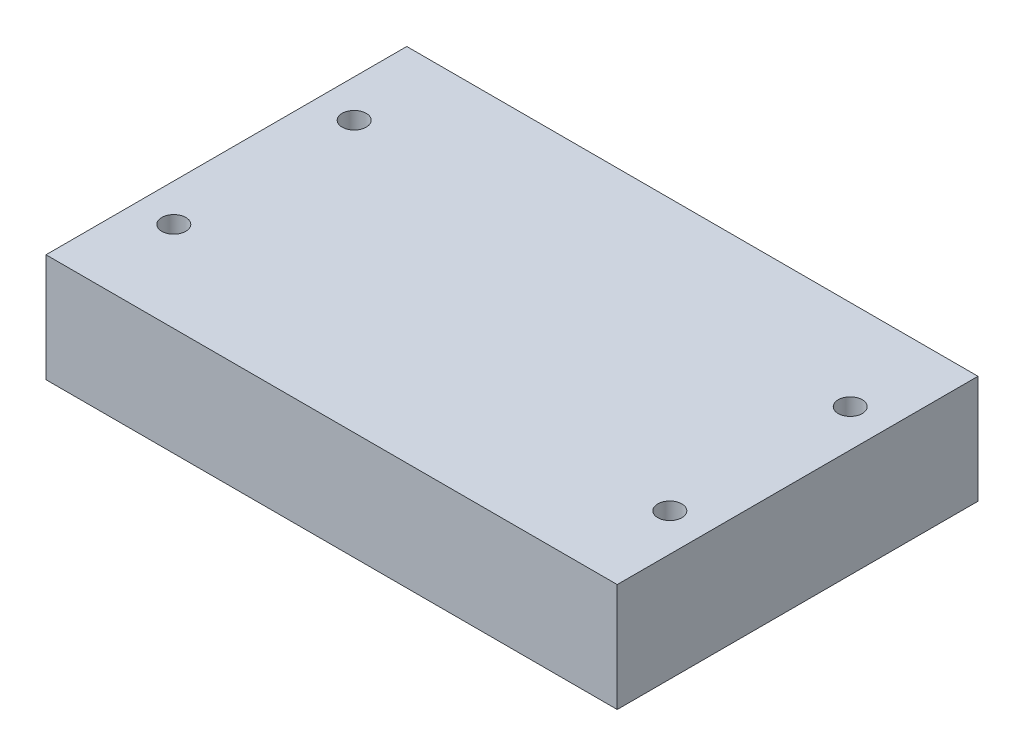
SolidWorks part; units mm, degrees
ref_plane "Plan de face" through (0, 0, 0) normal (0, 0, 1) x (1, 0, 0)
ref_plane "Plan de dessus" through (0, 0, 0) normal (0, 1, 0) x (1, 0, 0)
ref_plane "Plan de droite" through (0, 0, 0) normal (1, 0, 0) x (0, 0, -1)
sketch "Esquisse1" plane through (0, 0, 0) normal (0, 1, 0) x (1, 0, 0)
  line L0 (-52.1913, -9.9839) -> (-45.9413, -9.9839) construction
  line L1 (-52.1913, 35.0161) -> (42.8087, 35.0161)
  line L2 (-52.1913, 35.0161) -> (-52.1913, -24.9839)
  line L3 (-52.1913, -24.9839) -> (42.8087, -24.9839)
  line L4 (42.8087, 35.0161) -> (42.8087, -24.9839)
  line L5 (-45.9413, -9.9839) -> (36.5587, -9.9839) construction
  line L6 (36.5587, -9.9839) -> (42.8087, -9.9839) construction
  line L7 (-52.1913, 20.0161) -> (-45.9413, 20.0161) construction
  line L8 (-45.9413, 20.0161) -> (36.5587, 20.0161) construction
  line L9 (36.5587, 20.0161) -> (42.8087, 20.0161) construction
  line L10 (-45.9413, 35.0161) -> (-45.9413, 20.0161) construction
  line L11 (-45.9413, 20.0161) -> (-45.9413, -9.9839) construction
  line L12 (-45.9413, -9.9839) -> (-45.9413, -24.9839) construction
  line L13 (36.5587, 35.0161) -> (36.5587, 20.0161) construction
  line L14 (36.5587, 20.0161) -> (36.5587, -9.9839) construction
  line L15 (36.5587, -9.9839) -> (36.5587, -24.9839) construction
  circle A0 centre (-45.9413, 20.0161) radius 2
  circle A1 centre (36.5587, 20.0161) radius 2
  circle A2 centre (36.5587, -9.9839) radius 2
  circle A3 centre (-45.9413, -9.9839) radius 2
  dimension "D3" = 4
  dimension "D1" = 95
  dimension "D2" = 60
  dimension "D4" = 15
  dimension "D5" = 6.25
extrude "Boss.-Extru.1" add sketch "Esquisse1" along normal blind 18
sketch "Esquisse2" plane through (0, 0, 24.9839) normal (0, 0, 1) x (1, 0, 0)
  line L0 (-52.1913, 9) -> (-32.1913, 9) construction
  line L1 (-52.1913, 18) -> (-52.1913, 0) construction
  line L2 (-32.1913, 9) -> (22.8087, 9) construction
  line L3 (22.8087, 9) -> (42.8087, 9) construction
  line L4 (42.8087, 18) -> (42.8087, 0) construction
  dimension "D2" = 20
